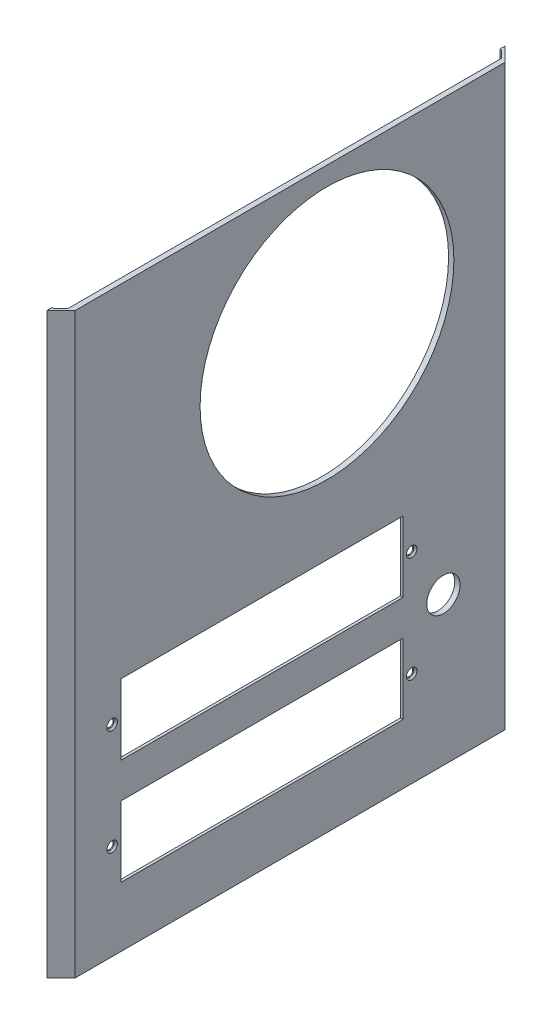
SolidWorks part; units mm, degrees
ref_plane "Front Plane" through (0, 0, 0) normal (0, 0, 1) x (1, 0, 0)
ref_plane "Top Plane" through (0, 0, 0) normal (0, 1, 0) x (1, 0, 0)
ref_plane "Right Plane" through (0, 0, 0) normal (1, 0, 0) x (0, 0, -1)
sketch "Sketch1" plane through (0, 0, 0) normal (1, 0, 0) x (0, 0, -1)
  line L1 (82.5383, 104.14) -> (-82.5383, 104.14)
  line L2 (82.5383, 104.14) -> (82.5383, -104.14)
  line L3 (82.5383, -104.14) -> (-82.5383, -104.14)
  line L4 (-82.5383, 104.14) -> (-82.5383, -104.14)
  point P4 (0, -104.14)
  point P6 (-82.5383, 0)
  dimension "D1" = 165.0767
  dimension "D2" = 208.28
extrude "Boss-Extrude1" add sketch "Sketch1" along normal blind 5.08
sketch "Sketch3" plane through (0, 0, 0) normal (-1, 0, 0) x (0, 0, 1)
  line L0 (-80.6333, -12.2767) -> (-80.6333, -78.74)
  line L2 (-80.6333, 104.14) -> (-80.6333, -3.81)
  line L4 (80.6333, 78.74) -> (80.6333, -3.81)
  line L7 (-82.5383, -104.14) -> (-82.5383, 104.14) construction
  line L14 (80.6333, 78.74) -> (71.1083, 78.74)
  line L15 (71.1083, 87.2067) -> (71.1083, 78.74)
  line L18 (80.6333, -78.74) -> (71.1083, -78.74)
  line L19 (71.1083, -87.2067) -> (71.1083, -78.74)
  line L22 (-80.6333, -78.74) -> (-71.1083, -78.74)
  line L23 (-71.1083, -87.2067) -> (-71.1083, -78.74)
  line L24 (-80.6333, -3.81) -> (-71.1083, -3.81)
  line L26 (-80.6333, -12.2767) -> (-71.1083, -12.2767)
  line L27 (-71.1083, -3.81) -> (-71.1083, -12.2767)
  line L28 (80.6333, -3.81) -> (71.1083, -3.81)
  line L30 (80.6333, -12.2767) -> (71.1083, -12.2767)
  line L31 (71.1083, -3.81) -> (71.1083, -12.2767)
  line L32 (80.6333, -12.2767) -> (80.6333, -78.74)
  line L36 (-80.6333, 104.14) -> (80.6333, 104.14)
  line L37 (80.6333, 104.14) -> (80.6333, 87.2067)
  line L38 (80.6333, 87.2067) -> (71.1083, 87.2067)
  line L39 (-71.1083, -87.2067) -> (-80.6333, -87.2067)
  line L41 (-80.6333, -87.2067) -> (-80.6333, -104.14)
  line L42 (-80.6333, -104.14) -> (80.6333, -104.14)
  line L43 (80.6333, -104.14) -> (80.6333, -87.2067)
  line L44 (80.6333, -87.2067) -> (71.1083, -87.2067)
  line L45 (82.5383, -104.14) -> (-82.5383, -104.14) construction
  line L46 (-82.5383, 104.14) -> (82.5383, 104.14) construction
  point P41 (0, 104.14)
  dimension "D1" = 1.905
  dimension "D2" = 16.9333
  dimension "D3" = 8.4667
  dimension "D4" = 9.525
  dimension "D5" = 107.95
  dimension "D6" = 16.9333
extrude "Cut-Extrude1" cut sketch "Sketch3" against normal offset from surface (3.175 mm away) 1.905 up to face at (5.08, 0, 0)
sketch "Sketch8" plane through (5.08, 0, 0) normal (1, 0, 0) x (0, 0, -1)
  circle A0 centre (13.2883, 51.6767) radius 45.72
  dimension "D1" = 91.44
extrude "Cut-Extrude2" cut sketch "Sketch8" against normal up to next
sketch "Sketch9" plane through (5.08, 0, 0) normal (1, 0, 0) x (0, 0, -1)
  line L0 (40.6517, -44.45) -> (40.6517, -57.15) construction
  line L5 (-60.9483, -19.05) -> (40.6517, -19.05)
  line L6 (-60.9483, -19.05) -> (-60.9483, -44.45)
  line L7 (-60.9483, -44.45) -> (40.6517, -44.45)
  line L8 (40.6517, -19.05) -> (40.6517, -44.45)
  line L9 (-60.9483, -57.15) -> (40.6517, -57.15)
  line L10 (-60.9483, -57.15) -> (-60.9483, -82.55)
  line L11 (-60.9483, -82.55) -> (40.6517, -82.55)
  line L12 (40.6517, -57.15) -> (40.6517, -82.55)
  line L13 (-82.5383, -82.55) -> (-60.9483, -82.55) construction
  line L14 (55.2333, -50.8) -> (40.6517, -50.8) construction
  line L15 (82.5383, -104.14) -> (82.5383, 104.14) construction
  line L16 (-60.9483, -82.55) -> (-60.9483, -104.14) construction
  line L19 (-82.5383, 104.14) -> (-82.5383, -104.14) construction
  line L20 (-82.5383, -104.14) -> (82.5383, -104.14) construction
  circle A0 centre (55.2333, -50.8) radius 6
  point P13 (40.6517, -50.8)
  point P21 (-60.9483, -82.55)
  dimension "D7" = 12
  dimension "D1" = 101.6
  dimension "D2" = 25.4
  dimension "D3" = 12.7
  dimension "D4" = 21.59
  dimension "D5" = 21.59
  dimension "D6" = 21.59
  dimension "D8" = 27.305
extrude "Cut-Extrude3" cut sketch "Sketch9" against normal up to next
sketch "Sketch10" plane through (5.08, 0, 0) normal (1, 0, 0) x (0, 0, -1)
  line L0 (-64.1233, -31.75) -> (-60.9483, -31.75) construction
  line L1 (-60.9483, -19.05) -> (-60.9483, -44.45) construction
  line L2 (-64.1233, -69.85) -> (-60.9483, -69.85) construction
  line L3 (-60.9483, -57.15) -> (-60.9483, -82.55) construction
  line L4 (43.8267, -31.75) -> (40.6517, -31.75) construction
  line L5 (40.6517, -44.45) -> (40.6517, -19.05) construction
  line L6 (43.8267, -69.85) -> (40.6517, -69.85) construction
  line L7 (40.6517, -82.55) -> (40.6517, -57.15) construction
  point P0 (-64.1233, -69.85)
  point P1 (43.8267, -69.85)
  point P2 (43.8267, -31.75)
  point P3 (-64.1233, -31.75)
  dimension "D1" = 3.175
hole_wizard "M2 Clearance Hole1" positions "Sketch10" profile "Sketch11" hole size "M2" standard "ANSI Metric" end condition up to next
sketch "Sketch11" plane through (5.08, -69.85, 64.1233) normal (0, 1, 0) x (0, 0, -1)
  line L0 (0, 0) -> (0, 1.905)
  line L1 (0, 1.905) -> (1.3, 1.905)
  line L2 (1.3, 1.905) -> (1.3, 0.6)
  line L3 (1.3, 0.6) -> (1.9, 0)
  line L5 (1.9, 0) -> (0, 0)
  line L6 (-1.3, 0.6) -> (-1.9, 0) construction
  line L11 (0, -6.35) -> (0, 107.95) construction
  dimension "Thru Hole Dia." = 2.6
  dimension "Thru Hole Depth" = 1.905
  dimension "Near C'Sink Dia." = 3.8
  dimension "Near C'Sink Angle" = 90
sketch "Sketch12" plane through (3.175, 0, 0) normal (-1, 0, 0) x (0, 0, 1)
  line L0 (-40.6517, -16.51) -> (60.9483, -16.51)
  line L1 (60.9483, -16.51) -> (65.0346, -23.6827)
  line L2 (65.0346, -39.8173) -> (60.9483, -46.99)
  line L3 (60.9483, -46.99) -> (-40.6517, -46.99)
  line L4 (-40.6517, -46.99) -> (-44.7379, -39.8173)
  line L5 (-44.7379, -23.6827) -> (-40.6517, -16.51)
  line L6 (60.9483, -19.05) -> (60.9483, -44.45) construction
  line L7 (-40.6517, -44.45) -> (-40.6517, -19.05) construction
  line L8 (-40.6517, -16.51) -> (-40.6517, -19.05) construction
  line L9 (-80.6333, 104.14) -> (-80.6333, -3.81) construction
  line L10 (-80.6333, -50.8) -> (80.4333, -50.8) construction
  line L12 (60.9483, -44.45) -> (60.9483, -46.99) construction
  line L14 (-43.8267, -31.75) -> (-46.8747, -31.75) construction
  line L15 (64.1233, -31.75) -> (67.1713, -31.75) construction
  line L16 (64.1233, -69.85) -> (67.1713, -69.85) construction
  line L17 (-43.8267, -69.85) -> (-46.8747, -69.85) construction
  line L18 (60.9483, -57.15) -> (60.9483, -54.61) construction
  line L19 (-40.6517, -85.09) -> (-40.6517, -82.55) construction
  line L20 (-44.7379, -77.9173) -> (-40.6517, -85.09)
  line L21 (-40.6517, -54.61) -> (-44.7379, -61.7827)
  line L22 (60.9483, -54.61) -> (-40.6517, -54.61)
  line L23 (65.0346, -61.7827) -> (60.9483, -54.61)
  line L24 (60.9483, -85.09) -> (65.0346, -77.9173)
  line L25 (-40.6517, -85.09) -> (60.9483, -85.09)
  arc A0 (65.0346, -23.6827) -> (65.0346, -39.8173) centre (50.8739, -31.75) cw
  arc A1 (-44.7379, -39.8173) -> (-44.7379, -23.6827) centre (-30.5772, -31.75) cw
  arc A2 (-44.7379, -61.7827) -> (-44.7379, -77.9173) centre (-30.5772, -69.85) ccw
  circle A3 centre (64.1233, -31.75) radius 1.3 construction
  arc A4 (65.0346, -77.9173) -> (65.0346, -61.7827) centre (50.8739, -69.85) ccw
  circle A5 centre (-43.8267, -31.75) radius 1.3 construction
  circle A7 centre (-55.2333, -50.8) radius 6 construction
  point P23 (-55.2333, -50.8)
  dimension "D1" = 2.54
  dimension "D2" = 3.048
  dimension "D3" = 8.255
extrude "Cut-Extrude4" cut sketch "Sketch12" against normal blind 0.9525
sketch "Lettering Outline" plane through (5.08, 0, 0) normal (1, 0, 0) x (0, 0, -1)
  line L0 (-44.015, 97.3967) -> (13.2883, 97.3967) construction
  line L38 (-60.9483, 97.3967) -> (-44.015, 97.3967) construction
  line L39 (-60.9483, 97.3967) -> (-60.9483, 80.4633) construction
  line L40 (-60.9483, 80.4633) -> (-44.015, 80.4633) construction
  line L41 (-44.015, 97.3967) -> (-44.015, 80.4633) construction
  line L42 (-60.9483, 78.77) -> (-44.015, 78.77) construction
  line L43 (-60.9483, 78.77) -> (-60.9483, 61.8367) construction
  line L44 (-60.9483, 61.8367) -> (-44.015, 61.8367) construction
  line L45 (-44.015, 78.77) -> (-44.015, 61.8367) construction
  line L46 (-60.9483, 60.1433) -> (-44.015, 60.1433) construction
  line L47 (-60.9483, 60.1433) -> (-60.9483, 43.21) construction
  line L48 (-60.9483, 43.21) -> (-44.015, 43.21) construction
  line L49 (-44.015, 60.1433) -> (-44.015, 43.21) construction
  line L50 (-60.9483, 41.5167) -> (-44.015, 41.5167) construction
  line L51 (-60.9483, 41.5167) -> (-60.9483, 24.5833) construction
  line L52 (-60.9483, 24.5833) -> (-44.015, 24.5833) construction
  line L53 (-44.015, 41.5167) -> (-44.015, 24.5833) construction
  line L54 (-60.9483, 22.89) -> (-44.015, 22.89) construction
  line L55 (-60.9483, 22.89) -> (-60.9483, 5.9567) construction
  line L56 (-60.9483, 5.9567) -> (-44.015, 5.9567) construction
  line L57 (-44.015, 22.89) -> (-44.015, 5.9567) construction
  line L58 (-60.9483, 80.4633) -> (-60.9483, 78.77) construction
  line L59 (-60.9483, 61.8367) -> (-60.9483, 60.1433) construction
  line L60 (-60.9483, 43.21) -> (-60.9483, 41.5167) construction
  line L61 (-60.9483, 24.5833) -> (-60.9483, 22.89) construction
  line L62 (-60.9483, -19.05) -> (-60.9483, -44.45) construction
  line L63 (-44.015, 5.9567) -> (13.2883, 5.9567) construction
  line L64 (-60.9483, 83.85) -> (-57.5617, 83.85) construction
  line L65 (-57.5617, 83.85) -> (-54.175, 83.85) construction
  line L66 (-54.175, 83.85) -> (-50.7883, 83.85) construction
  line L67 (-50.7883, 83.85) -> (-47.4017, 83.85) construction
  line L68 (-47.4017, 83.85) -> (-44.015, 83.85) construction
  line L69 (-57.5617, 80.4633) -> (-57.5617, 83.85) construction
  line L70 (-57.5617, 83.85) -> (-57.5617, 87.2367) construction
  line L71 (-57.5617, 87.2367) -> (-57.5617, 90.6233) construction
  line L72 (-57.5617, 90.6233) -> (-57.5617, 94.01) construction
  line L73 (-57.5617, 94.01) -> (-57.5617, 97.3967) construction
  line L74 (-60.9483, 65.2233) -> (-57.5617, 65.2233) construction
  line L75 (-57.5617, 65.2233) -> (-54.175, 65.2233) construction
  line L76 (-54.175, 65.2233) -> (-50.7883, 65.2233) construction
  line L77 (-50.7883, 65.2233) -> (-47.4017, 65.2233) construction
  line L78 (-47.4017, 65.2233) -> (-44.015, 65.2233) construction
  line L79 (-57.5617, 61.8367) -> (-57.5617, 65.2233) construction
  line L80 (-57.5617, 65.2233) -> (-57.5617, 68.61) construction
  line L81 (-57.5617, 68.61) -> (-57.5617, 71.9967) construction
  line L82 (-57.5617, 71.9967) -> (-57.5617, 75.3833) construction
  line L83 (-57.5617, 75.3833) -> (-57.5617, 78.77) construction
  line L84 (-60.9483, 46.5967) -> (-57.5617, 46.5967) construction
  line L85 (-57.5617, 46.5967) -> (-54.175, 46.5967) construction
  line L86 (-54.175, 46.5967) -> (-50.7883, 46.5967) construction
  line L87 (-50.7883, 46.5967) -> (-47.4017, 46.5967) construction
  line L88 (-47.4017, 46.5967) -> (-44.015, 46.5967) construction
  line L89 (-57.5617, 43.21) -> (-57.5617, 46.5967) construction
  line L90 (-57.5617, 46.5967) -> (-57.5617, 49.9833) construction
  line L91 (-57.5617, 49.9833) -> (-57.5617, 53.37) construction
  line L92 (-57.5617, 53.37) -> (-57.5617, 56.7567) construction
  line L93 (-57.5617, 56.7567) -> (-57.5617, 60.1433) construction
  line L94 (-60.9483, 27.97) -> (-57.5617, 27.97) construction
  line L95 (-57.5617, 27.97) -> (-54.175, 27.97) construction
  line L96 (-54.175, 27.97) -> (-50.7883, 27.97) construction
  line L97 (-50.7883, 27.97) -> (-47.4017, 27.97) construction
  line L98 (-47.4017, 27.97) -> (-44.015, 27.97) construction
  line L99 (-57.5617, 24.5833) -> (-57.5617, 27.97) construction
  line L100 (-57.5617, 27.97) -> (-57.5617, 31.3567) construction
  line L101 (-57.5617, 31.3567) -> (-57.5617, 34.7433) construction
  line L102 (-57.5617, 34.7433) -> (-57.5617, 38.13) construction
  line L103 (-57.5617, 38.13) -> (-57.5617, 41.5167) construction
  line L104 (-60.9483, 9.3433) -> (-57.5617, 9.3433) construction
  line L105 (-57.5617, 9.3433) -> (-54.175, 9.3433) construction
  line L106 (-54.175, 9.3433) -> (-50.7883, 9.3433) construction
  line L107 (-50.7883, 9.3433) -> (-47.4017, 9.3433) construction
  line L108 (-47.4017, 9.3433) -> (-44.015, 9.3433) construction
  line L109 (-57.5617, 5.9567) -> (-57.5617, 9.3433) construction
  line L110 (-57.5617, 9.3433) -> (-57.5617, 12.73) construction
  line L111 (-57.5617, 12.73) -> (-57.5617, 16.1167) construction
  line L112 (-57.5617, 16.1167) -> (-57.5617, 19.5033) construction
  line L113 (-57.5617, 19.5033) -> (-57.5617, 22.89) construction
  circle A0 centre (13.2883, 51.6767) radius 45.72 construction
  dimension "D2" = 91.44
  dimension "D1" = 16.9333
sketch "Sketch13" plane through (0, 0, 0) normal (-1, 0, 0) x (0, 0, 1)
  line L5 (-71.1083, -3.81) -> (-71.1083, -12.2767) construction
  line L7 (-78.5167, -8.0433) -> (-75.3417, -4.8683)
  line L10 (-78.5167, -8.0433) -> (-75.3417, -11.2183)
  line L11 (-75.3417, -4.8683) -> (-72.1667, -8.0433)
  line L12 (-75.3417, -11.2183) -> (-72.1667, -8.0433)
  line L13 (-78.5167, -8.0433) -> (-72.1667, -8.0433) construction
  line L14 (-75.3417, -4.8683) -> (-75.3417, -11.2183) construction
  line L15 (-71.1083, -12.2767) -> (-71.1083, -3.81) construction
  line L16 (-78.5167, -82.9733) -> (-75.3417, -79.7983)
  line L17 (-78.5167, -82.9733) -> (-75.3417, -86.1483)
  line L18 (-75.3417, -79.7983) -> (-72.1667, -82.9733)
  line L19 (-75.3417, -86.1483) -> (-72.1667, -82.9733)
  line L20 (-78.5167, -82.9733) -> (-72.1667, -82.9733) construction
  line L21 (-75.3417, -79.7983) -> (-75.3417, -86.1483) construction
  line L22 (-71.1083, -87.2067) -> (-71.1083, -78.74) construction
  line L23 (72.1667, -82.9733) -> (75.3417, -79.7983)
  line L24 (72.1667, -82.9733) -> (75.3417, -86.1483)
  line L25 (75.3417, -79.7983) -> (78.5167, -82.9733)
  line L26 (75.3417, -86.1483) -> (78.5167, -82.9733)
  line L27 (72.1667, -82.9733) -> (78.5167, -82.9733) construction
  line L28 (75.3417, -79.7983) -> (75.3417, -86.1483) construction
  line L30 (72.1667, -8.0433) -> (75.3417, -4.8683)
  line L31 (72.1667, -8.0433) -> (75.3417, -11.2183)
  line L32 (75.3417, -4.8683) -> (78.5167, -8.0433)
  line L33 (75.3417, -11.2183) -> (78.5167, -8.0433)
  line L34 (72.1667, -8.0433) -> (78.5167, -8.0433) construction
  line L35 (75.3417, -4.8683) -> (75.3417, -11.2183) construction
  line L36 (72.1667, 82.9733) -> (75.3417, 86.1483)
  line L37 (72.1667, 82.9733) -> (75.3417, 79.7983)
  line L38 (75.3417, 86.1483) -> (78.5167, 82.9733)
  line L39 (75.3417, 79.7983) -> (78.5167, 82.9733)
  line L40 (72.1667, 82.9733) -> (78.5167, 82.9733) construction
  line L41 (75.3417, 86.1483) -> (75.3417, 79.7983) construction
  line L43 (71.1083, 78.74) -> (71.1083, 87.2067) construction
  point P8 (-75.3417, -8.0433)
  point P13 (-71.1083, -8.0433)
  point P19 (-75.3417, -82.9733)
  point P21 (-71.1083, -82.9733)
  point P27 (75.3417, -82.9733)
  point P35 (75.3417, -8.0433)
  point P36 (75.3417, 82.9733)
  dimension "D1" = 4.2333
  dimension "D3" = 4.2333
extrude "Cut-Extrude7" cut sketch "Sketch13" against normal blind 4.2333
chamfer "Chamfer1" distance 0.635 angle 45 40 edges at (4.2333, 84.5608, 73.7542) (4.2333, 84.5608, 76.9292) (4.2333, 81.3858, 76.9292) (4.2333, 81.3858, 73.7542) (4.2333, -6.4558, 73.7542) (4.2333, -6.4558, 76.9292) (4.2333, -9.6308, 76.9292) (4.2333, -9.6308, 73.7542) (4.2333, -81.3858, 73.7542) (4.2333, -81.3858, 76.9292) (4.2333, -84.5608, 76.9292) (4.2333, -84.5608, 73.7542) (4.2333, -81.3858, -76.9292) (4.2333, -81.3858, -73.7542) (4.2333, -84.5608, -73.7542) (4.2333, -84.5608, -76.9292) (4.2333, -6.4558, -76.9292) (4.2333, -6.4558, -73.7542) (4.2333, -9.6308, -73.7542) (4.2333, -9.6308, -76.9292) (0, 81.3858, 73.7542) (0, 81.3858, 76.9292) (0, 84.5608, 76.9292) (0, 84.5608, 73.7542) (0, -9.6308, 73.7542) (0, -9.6308, 76.9292) (0, -6.4558, 73.7542) (0, -6.4558, 76.9292) (0, -84.5608, 76.9292) (0, -81.3858, 76.9292) (0, -84.5608, 73.7542) (0, -81.3858, 73.7542) (0, -84.5608, -76.9292) (0, -84.5608, -73.7542) (0, -81.3858, -73.7542) (0, -81.3858, -76.9292) (0, -9.6308, -76.9292) (0, -9.6308, -73.7542) (0, -6.4558, -73.7542) (0, -6.4558, -76.9292)
chamfer "Chamfer2" distance 2.54 angle 45 7 edges at (3.175, 95.6733, 80.6333) (3.175, 37.465, 80.6333) (3.175, -45.5083, 80.6333) (3.175, -95.6733, 80.6333) (3.175, -95.6733, -80.6333) (3.175, -45.5083, -80.6333) (3.175, 50.165, -80.6333)
chamfer "Chamfer3" distance 5.08 angle 45 2 edges at (5.08, 0, -82.5383) (5.08, 0, 82.5383)
